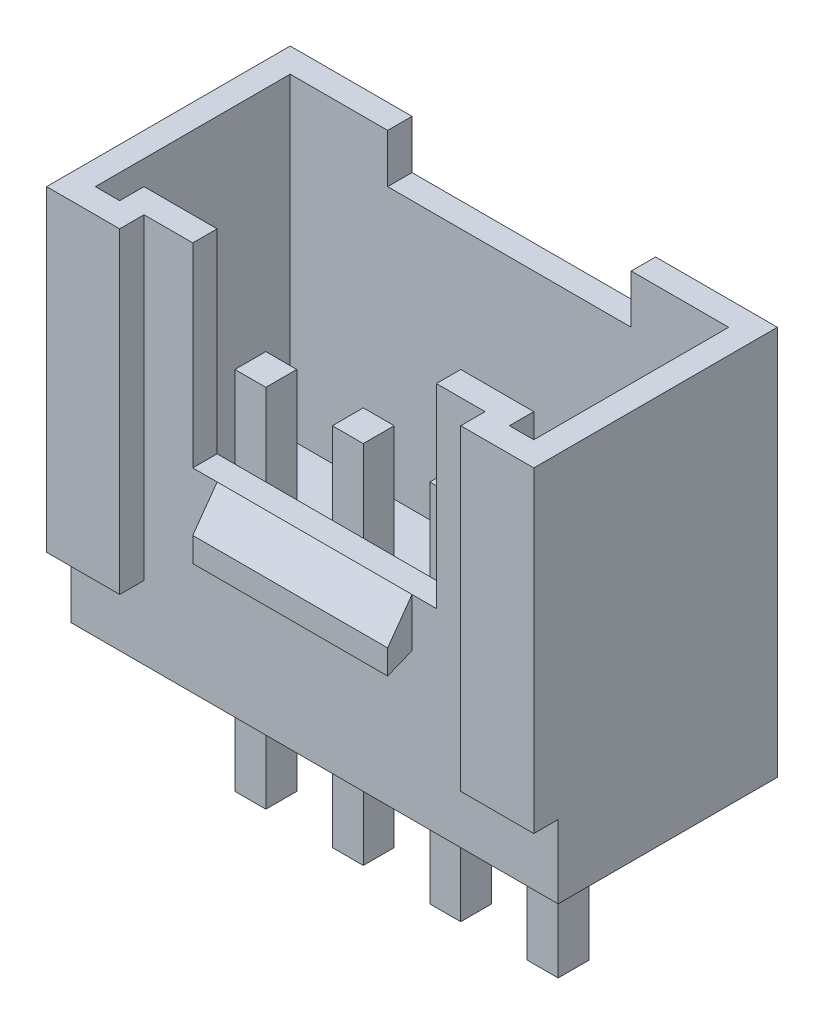
SolidWorks part; units mm, degrees
ref_plane "Front Plane" through (0, 0, 0) normal (0, 0, 1) x (1, 0, 0)
ref_plane "Top Plane" through (0, 0, 0) normal (0, 1, 0) x (1, 0, 0)
ref_plane "Right Plane" through (0, 0, 0) normal (1, 0, 0) x (0, 0, -1)
sketch "Sketch1" plane through (0, 0, 0) normal (0, 1, 0) x (1, 0, 0)
  line L0 (8.5, 0) -> (10, 0)
  line L1 (0, 0) -> (1.5, 0)
  line L2 (0, 0) -> (0, 5)
  line L3 (0, 5) -> (10, 5)
  line L4 (10, 0) -> (10, 5)
  line L6 (1.5, 0) -> (1.5, 0.5)
  line L7 (1.5, 0.5) -> (8.5, 0.5)
  line L8 (8.5, 0) -> (8.5, 0.5)
  line L10 (0.5, 4.5) -> (9.5, 4.5)
  line L11 (0.5, 4.5) -> (0.5, 1.5385)
  line L12 (1, 1) -> (9, 1)
  line L13 (9.5, 4.5) -> (9.5, 1.5288)
  line L15 (9.5, 1.5288) -> (9.5, 0.5)
  line L16 (9.5, 0.5) -> (9, 0.5)
  line L17 (9, 1) -> (9, 0.5)
  line L19 (0.5, 1.5385) -> (0.5, 0.5)
  line L20 (0.5, 0.5) -> (1, 0.5)
  line L21 (1, 1) -> (1, 0.5)
  point P9 (5, 0.5)
  point P10 (5, 5)
  point P21 (10, 2.5)
  dimension "D1" = 0.5
  dimension "D2" = 0.5
  dimension "D3" = 0.5
  dimension "D4" = 0.5
  dimension "D5" = 0.5
  dimension "D6" = 0.5
  dimension "D7" = 10
  dimension "D8" = 5
  dimension "D9" = 0.5
  dimension "D10" = 1
extrude "Sides" add sketch "Sketch1" along normal blind 8
sketch "Sketch2" plane through (0, 0, -0.5) normal (0, 0, 1) x (1, 0, 0)
  line L0 (1.5, 8) -> (8.5, 8) construction
  line L1 (2.5, 8) -> (7.5, 8)
  line L2 (2.5, 8) -> (2.5, 4)
  line L3 (2.5, 4) -> (7.5, 4)
  line L4 (7.5, 8) -> (7.5, 4)
  line L5 (1.5, 0) -> (8.5, 0) construction
  point P6 (5, 8)
  point P9 (5, 0)
  dimension "D1" = 4
  dimension "D2" = 5
extrude "Front cut" cut sketch "Sketch2" against normal up to surface (0.5 mm away) up to face at (5, 4, -1)
sketch "Sketch3" plane through (0, 0, -5) normal (0, 0, -1) x (-1, 0, 0)
  line L0 (-10, 8) -> (0, 8) construction
  line L1 (-2.5, 8) -> (-7.5, 8)
  line L2 (-2.5, 8) -> (-2.5, 7)
  line L3 (-2.5, 7) -> (-7.5, 7)
  line L4 (-7.5, 8) -> (-7.5, 7)
  line L5 (-10, 0) -> (0, 0) construction
  point P6 (-5, 8)
  point P9 (-5, 0)
  dimension "D1" = 5
  dimension "D2" = 1
extrude "Back cut" cut sketch "Sketch3" against normal up to next
extrude "Base" add sketch "Sketch1<2>" along normal blind 0.5 contours L21 L12 L17 L16 L15 L13 L10 L11 L19 L20 region at (5, 0, -2.7188)
sketch "Sketch1<2>" plane through (0, 0, 0) normal (0, 1, 0) x (1, 0, 0) same geometry as "Sketch1"
sketch "Sketch4" plane through (0, 0.5, 0) normal (0, 1, 0) x (1, 0, 0)
  line L0 (0.5, 4.5) -> (0.5, 0.5) construction
  line L1 (1.6825, 2.8175) -> (2.3175, 2.8175)
  line L2 (1.6825, 2.8175) -> (1.6825, 2.1825)
  line L3 (1.6825, 2.1825) -> (2.3175, 2.1825)
  line L4 (2.3175, 2.8175) -> (2.3175, 2.1825)
  line L5 (3.6825, 2.8175) -> (3.6825, 2.1825)
  line L6 (3.6825, 2.8175) -> (4.3175, 2.8175)
  line L7 (4.3175, 2.8175) -> (4.3175, 2.1825)
  line L8 (3.6825, 2.1825) -> (4.3175, 2.1825)
  line L9 (5.6825, 2.8175) -> (5.6825, 2.1825)
  line L10 (5.6825, 2.8175) -> (6.3175, 2.8175)
  line L11 (6.3175, 2.8175) -> (6.3175, 2.1825)
  line L12 (5.6825, 2.1825) -> (6.3175, 2.1825)
  line L13 (7.6825, 2.8175) -> (7.6825, 2.1825)
  line L14 (7.6825, 2.8175) -> (8.3175, 2.8175)
  line L15 (8.3175, 2.8175) -> (8.3175, 2.1825)
  line L16 (7.6825, 2.1825) -> (8.3175, 2.1825)
  line L17 (1.6825, 2.8175) -> (3.6825, 2.8175) construction
  line L18 (1.6825, 2.5) -> (8.3175, 2.5) construction
  line L19 (2.5, 1) -> (7.5, 1) construction
  point P6 (0.5, 2.5)
  point P7 (2.3175, 2.5)
  point P24 (5, 2.5)
  point P27 (5, 1)
  dimension "D1" = 0.635
  dimension "D3" = 2
  dimension "D2" = 4
extrude "Pins" add sketch "Sketch4" along normal blind 4 and the other way blind 3.5
ref_plane "Plane1" through (5, 0, 0) normal (1, 0, 0) x (0, 0, -1)
sketch "Sketch5" plane through (5, 0, 0) normal (1, 0, 0) x (0, 0, -1)
  line L0 (0.5, 4) -> (0.5, 3)
  line L1 (0.5, 3) -> (0, 2.8)
  line L2 (0, 2.8) -> (0, 3.3)
  line L3 (0, 3.3) -> (0.5, 4)
  point P2 (0, 0)
  point P5 (-0.2141, 2.8)
  point P7 (0.5, 2.9528)
  dimension "D1" = 0.5
  dimension "D2" = 0.5
  dimension "D3" = 1.2
  dimension "D4" = 1
extrude "Clip" add sketch "Sketch5" along normal blind 2 and the other way blind 2
sketch "Sketch6" plane through (5, 0, 0) normal (1, 0, 0) x (0, 0, -1)
  line L1 (0, 0) -> (0.5, 0)
  line L2 (0, 0) -> (0, 1.5)
  line L3 (0, 1.5) -> (0.5, 1.5)
  line L4 (0.5, 0) -> (0.5, 1.5)
  dimension "D1" = 0.5
  dimension "D2" = 1.5
extrude "Front trim" cut sketch "Sketch6" against normal through all both and the other way through all
extrude "Boss-Extrude4" add sketch "Sketch1<4>" along normal blind 1.51 contours L21 L12 L17 L16 L15 L13 L10 L11 L19 L20 region at (5, 0, -2.7188)
sketch "Sketch1<4>" plane through (0, 0, 0) normal (0, 1, 0) x (1, 0, 0) same geometry as "Sketch1"
